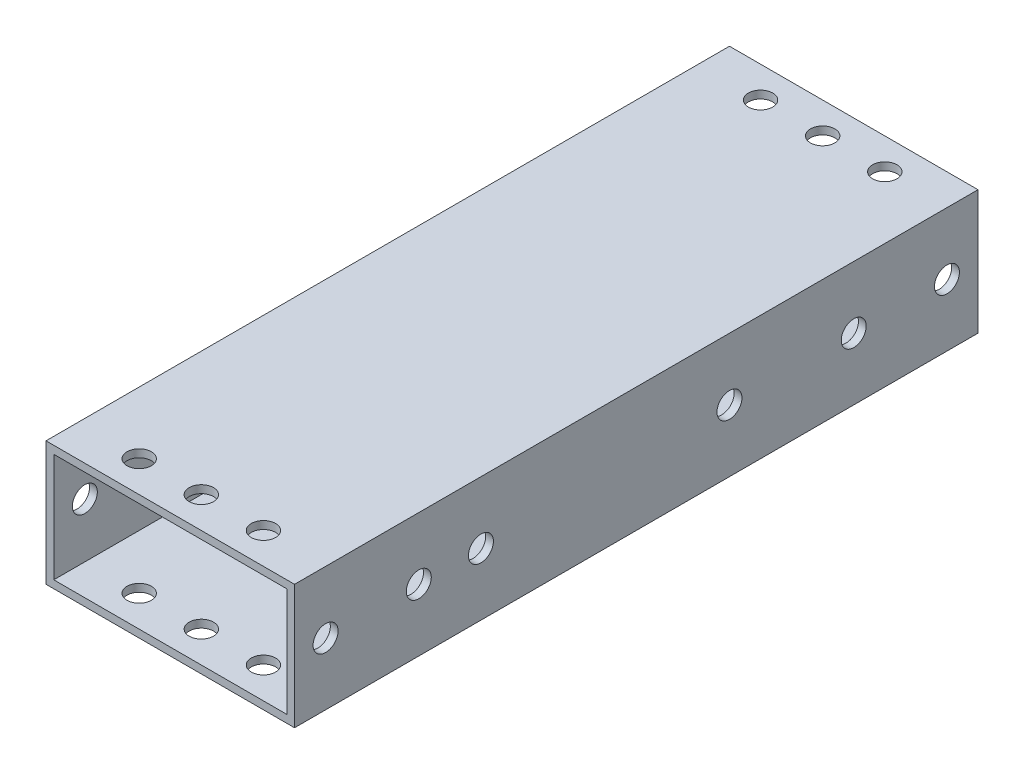
SolidWorks part; units mm, degrees
material "6061-T6 (SS)"
ref_plane "Front Plane" through (0, 0, 0) normal (0, 0, 1) x (1, 0, 0)
ref_plane "Top Plane" through (0, 0, 0) normal (0, 1, 0) x (1, 0, 0)
ref_plane "Right Plane" through (0, 0, 0) normal (1, 0, 0) x (0, 0, -1)
sketch "Sketch1" plane through (0, 0, 0) normal (0, 0, 1) x (1, 0, 0)
  line L0 (-23.8125, 11.1125) -> (23.8125, 11.1125)
  line L1 (-25.4, -12.7) -> (25.4, -12.7)
  line L2 (-25.4, -12.7) -> (-25.4, 12.7)
  line L3 (-25.4, 12.7) -> (25.4, 12.7)
  line L4 (25.4, -12.7) -> (25.4, 12.7)
  line L5 (-25.4, -12.7) -> (25.4, 12.7) construction
  line L6 (-25.4, 12.7) -> (25.4, -12.7) construction
  line L7 (23.8125, -11.1125) -> (23.8125, 11.1125)
  line L8 (-23.8125, -11.1125) -> (23.8125, -11.1125)
  line L9 (-23.8125, -11.1125) -> (-23.8125, 11.1125)
  point P0 (0, 0)
  dimension "D1" = 50.8
  dimension "D2" = 25.4
  dimension "D3" = 1.5875
extrude "Boss-Extrude1" add sketch "Sketch1" along normal mid plane 139.7
sketch "Sketch2" plane through (0, 12.7, 0) normal (0, 1, 0) x (1, 0, 0)
  line L0 (25.4, 69.85) -> (-25.4, 69.85) construction
  line L1 (25.4, 0) -> (-25.4, 0) construction
  line L2 (25.4, -69.85) -> (25.4, 69.85) construction
  line L3 (-25.4, -69.85) -> (-25.4, 69.85) construction
  circle A0 centre (-12.7, 63.5) radius 2.4892
  circle A1 centre (0, 63.5) radius 2.4892
  circle A2 centre (12.7, 63.5) radius 2.4892
  circle A3 centre (12.7, -63.5) radius 2.4892
  circle A4 centre (0, -63.5) radius 2.4892
  circle A5 centre (-12.7, -63.5) radius 2.4892
  dimension "D4" = 4.9784
  dimension "D1" = 12.7
  dimension "D2" = 12.7
  dimension "D3" = 6.35
extrude "Cut-Extrude1" cut sketch "Sketch2" against normal through all
sketch "Sketch3" plane through (-25.4, 0, 0) normal (-1, 0, 0) x (0, 0, 1)
  line L0 (-69.85, 12.7) -> (-69.85, -12.7) construction
  line L1 (0, 12.7) -> (0, -12.7) construction
  line L2 (69.85, 12.7) -> (-69.85, 12.7) construction
  line L3 (69.85, -12.7) -> (-69.85, -12.7) construction
  line L4 (69.85, 12.7) -> (69.85, -12.7) construction
  circle A0 centre (-63.5, 0) radius 2.5527
  circle A1 centre (63.5, 0) radius 2.5527
  circle A4 centre (31.75, 0) radius 2.5527
  circle A5 centre (44.45, 0) radius 2.5527
  dimension "D1" = 5.1054
  dimension "D3" = 12.7
  dimension "D4" = 25.4
  dimension "D2" = 6.35
extrude "Cut-Extrude2" cut sketch "Sketch3" against normal through all contours A5 | A1 | A4 | A0
sketch "Sketch5" plane through (25.4, 0, 0) normal (1, 0, 0) x (0, 0, -1)
  line L0 (69.85, -12.7) -> (69.85, 12.7) construction
  circle A1 centre (44.45, 0) radius 2.5527
  circle A2 centre (19.05, 0) radius 2.5527
  dimension "D1" = 25.4
  dimension "D3" = 5.1054
  dimension "D4" = 25.4
extrude "Cut-Extrude3" cut sketch "Sketch5" against normal through all
